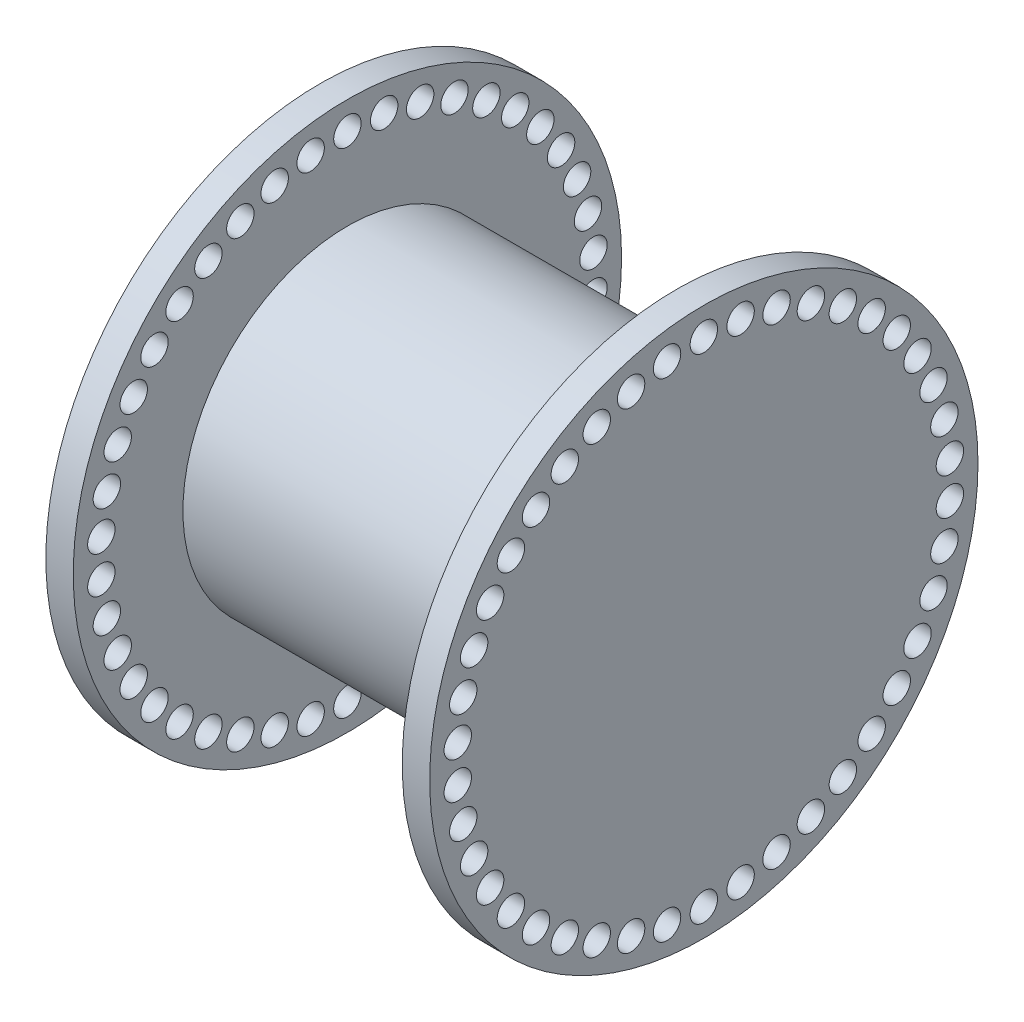
SolidWorks part; units mm, degrees
ref_plane "Front Plane" through (0, 0, 0) normal (0, 0, 1) x (1, 0, 0)
ref_plane "Top Plane" through (0, 0, 0) normal (0, 1, 0) x (1, 0, 0)
ref_plane "Right Plane" through (0, 0, 0) normal (1, 0, 0) x (0, 0, -1)
ref_axis "Axis1" through (-24.4475, 0, 0) along (1, 0, 0)
sketch "Sketch1" plane through (0, 0, 0) normal (1, 0, 0) x (0, 0, -1)
  line L0 (0, 31.75) -> (0, -31.75) construction
  line L1 (31.75, 0) -> (-31.75, 0) construction
  circle A0 centre (0, 0) radius 19.05
  circle A1 centre (0, 0) radius 31.75
  circle A2 centre (0, 28.575) radius 1.5875
  circle A3 centre (4.2589, 28.2558) radius 1.5875
  circle A4 centre (8.4226, 27.3055) radius 1.5875
  circle A5 centre (12.3982, 25.7452) radius 1.5875
  circle A6 centre (16.0969, 23.6098) radius 1.5875
  circle A7 centre (19.4359, 20.947) radius 1.5875
  circle A8 centre (22.3408, 17.8162) radius 1.5875
  circle A9 centre (24.7467, 14.2875) radius 1.5875
  circle A10 centre (26.5997, 10.4396) radius 1.5875
  circle A11 centre (27.8586, 6.3585) radius 1.5875
  circle A12 centre (28.4951, 2.1354) radius 1.5875
  circle A13 centre (28.4951, -2.1354) radius 1.5875
  circle A14 centre (27.8586, -6.3585) radius 1.5875
  circle A15 centre (26.5997, -10.4396) radius 1.5875
  circle A16 centre (24.7467, -14.2875) radius 1.5875
  circle A17 centre (22.3408, -17.8162) radius 1.5875
  circle A18 centre (19.4359, -20.947) radius 1.5875
  circle A19 centre (16.0969, -23.6098) radius 1.5875
  circle A20 centre (12.3982, -25.7452) radius 1.5875
  circle A21 centre (8.4226, -27.3055) radius 1.5875
  circle A22 centre (4.2589, -28.2558) radius 1.5875
  circle A23 centre (0, -28.575) radius 1.5875
  circle A24 centre (-4.2589, -28.2558) radius 1.5875
  circle A25 centre (-8.4226, -27.3055) radius 1.5875
  circle A26 centre (-12.3982, -25.7452) radius 1.5875
  circle A27 centre (-16.0969, -23.6098) radius 1.5875
  circle A28 centre (-19.4359, -20.947) radius 1.5875
  circle A29 centre (-22.3408, -17.8162) radius 1.5875
  circle A30 centre (-24.7467, -14.2875) radius 1.5875
  circle A31 centre (-26.5997, -10.4396) radius 1.5875
  circle A32 centre (-27.8586, -6.3585) radius 1.5875
  circle A33 centre (-28.4951, -2.1354) radius 1.5875
  circle A34 centre (-28.4951, 2.1354) radius 1.5875
  circle A35 centre (-27.8586, 6.3585) radius 1.5875
  circle A36 centre (-26.5997, 10.4396) radius 1.5875
  circle A37 centre (-24.7467, 14.2875) radius 1.5875
  circle A38 centre (-22.3408, 17.8162) radius 1.5875
  circle A39 centre (-19.4359, 20.947) radius 1.5875
  circle A40 centre (-16.0969, 23.6098) radius 1.5875
  circle A41 centre (-12.3982, 25.7452) radius 1.5875
  circle A42 centre (-8.4226, 27.3055) radius 1.5875
  circle A43 centre (-4.2589, 28.2558) radius 1.5875
  point P102 (0, 0)
  dimension "D1" = 3.175
  dimension "D2" = 63.5
  dimension "D3" = 38.1
  dimension "D4" = 3.175
  dimension "D5" = 42
extrude "Boss-Extrude1" add sketch "Sketch1" along normal mid plane 44.45 contours A0
extrude "Boss-Extrude2" add sketch "Sketch1<3>" against normal blind 3.175 from surface contours A1 A0 region at (0, 0, 30.852) starting at face at (22.225, 0, -19.05)
sketch "Sketch1<3>" plane through (0, 0, 0) normal (1, 0, 0) x (0, 0, -1) same geometry as "Sketch1"
extrude "Boss-Extrude3" add sketch "Sketch1<4>" along normal blind 3.175 from surface starting at face at (-22.225, 0, -19.05)
sketch "Sketch1<4>" plane through (0, 0, 0) normal (1, 0, 0) x (0, 0, -1) same geometry as "Sketch1"
ref_axis "Axis2" through (19.05, 2.1354, 28.4951) along (1, 0, 0)
